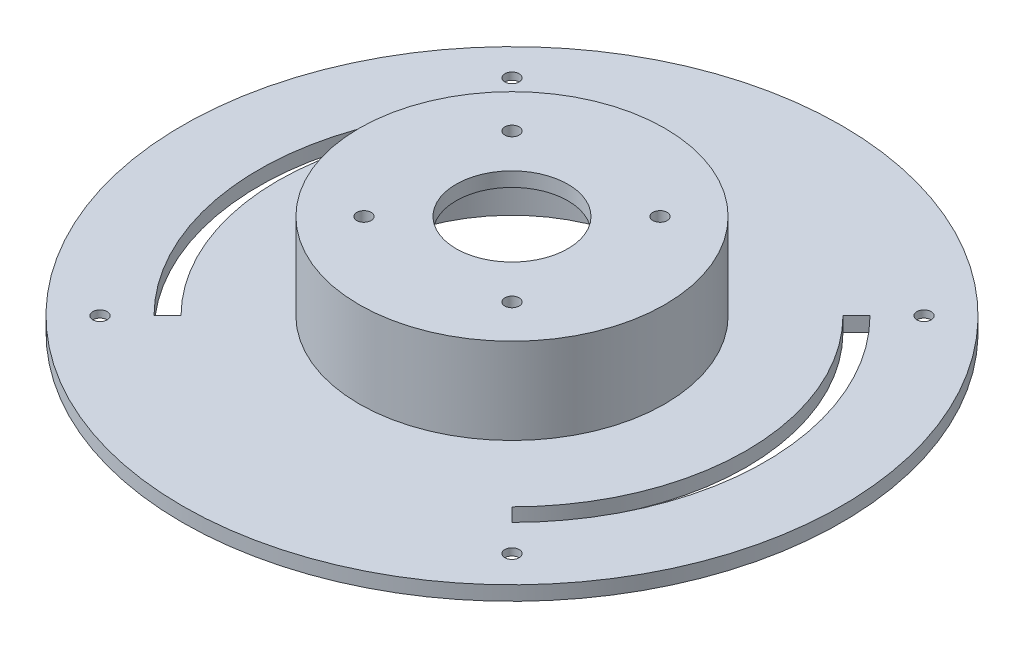
SolidWorks part; units mm, degrees
ref_plane "Front Plane" through (0, 0, 0) normal (0, 0, 1) x (1, 0, 0)
ref_plane "Top Plane" through (0, 0, 0) normal (0, 1, 0) x (1, 0, 0)
ref_plane "Right Plane" through (0, 0, 0) normal (1, 0, 0) x (0, 0, -1)
sketch "Sketch1" plane through (0, 0, 0) normal (0, 1, 0) x (1, 0, 0)
  circle A0 centre (0, 0) radius 69
  dimension "D1" = 138
extrude "Boss-Extrude1" add sketch "Sketch1" along normal blind 3
sketch "Sketch2" plane through (0, 3, 0) normal (0, 1, 0) x (1, 0, 0)
  circle A0 centre (0, 0) radius 32
  dimension "D1" = 64
extrude "Boss-Extrude2" add sketch "Sketch2" along normal blind 18
sketch "Sketch3" plane through (0, 21, 0) normal (0, 1, 0) x (1, 0, 0)
  line L0 (0, 56.364) -> (0, -54.6297) construction
  line L1 (-45.6693, 0) -> (37.576, 0) construction
  circle A0 centre (0, 0) radius 11.7
  circle A1 centre (15.5, 15.5) radius 1.5
  circle A2 centre (-15.5, 15.5) radius 1.5
  circle A3 centre (15.5, -15.5) radius 1.5
  circle A4 centre (-15.5, -15.5) radius 1.5
  dimension "D1" = 23.4
  dimension "D2" = 3
  dimension "D3" = 15.5
  dimension "D4" = 15.5
extrude "Cut-Extrude1" cut sketch "Sketch3" against normal through all
ref_plane "Plane2" through (0, 0, 0) normal (0, -1, 0) x (-1, 0, 0)
sketch "Sketch6" plane through (0, 0, 0) normal (0, -1, 0) x (-1, 0, 0)
  circle A0 centre (0, 0) radius 30
  dimension "D1" = 60
extrude "Cut-Extrude3" cut sketch "Sketch6" against normal blind 18
sketch "Sketch7" plane through (0, 3, 0) normal (0, 1, 0) x (1, 0, 0)
  line L0 (0, 73.7068) -> (0, -77.7534) construction
  line L1 (-89.2189, 0) -> (93.0728, 0) construction
  line L2 (0, 0) -> (55.0633, 55.0633) construction
  line L3 (0, 0) -> (-61.1332, 61.1332) construction
  line L4 (0, 0) -> (-63.9579, -63.9579) construction
  line L5 (0, 0) -> (64.7945, -64.7945) construction
  line L6 (34.6482, 34.6482) -> (37.4767, 37.4767)
  line L7 (37.4767, -37.4767) -> (34.6482, -34.6482)
  line L8 (-37.4767, -37.4767) -> (-34.6482, -34.6482)
  line L9 (-34.6482, 34.6482) -> (-37.4767, 37.4767)
  arc A0 (34.6482, 34.6482) -> (34.6482, -34.6482) centre (0, 0) cw
  circle A1 centre (0, 0) radius 69 construction
  arc A2 (37.4767, 37.4767) -> (37.4767, -37.4767) centre (0, 0) cw
  arc A3 (-34.6482, 34.6482) -> (-34.6482, -34.6482) centre (0, 0) ccw
  arc A4 (-37.4767, 37.4767) -> (-37.4767, -37.4767) centre (0, 0) ccw
  circle A5 centre (43.1335, 43.1335) radius 1.5
  circle A6 centre (43.1335, -43.1335) radius 1.5
  circle A7 centre (-43.1335, -43.1335) radius 1.5
  circle A8 centre (-43.1335, 43.1335) radius 1.5
  point P24 (0, 0)
  point P25 (0, 0)
  dimension "D5" = 20
  dimension "D7" = 12
  dimension "D8" = 3
  dimension "D1" = 45
  dimension "D2" = 45
  dimension "D3" = 45
  dimension "D4" = 45
  dimension "D6" = 4
extrude "Cut-Extrude5" cut sketch "Sketch7" against normal through all
sketch "Sketch8" plane through (0, 0, 0) normal (0, -1, 0) x (1, 0, 0)
  line L0 (0, 119.0407) -> (0, -90.7373) construction
  line L1 (-103.8901, 0) -> (87.907, 0) construction
  circle A0 centre (-43.1335, 43.1335) radius 4.05
  circle A1 centre (43.1335, 43.1335) radius 4.05
  circle A2 centre (43.1335, -43.1335) radius 4.05
  circle A3 centre (-43.1335, -43.1335) radius 4.05
  dimension "D1" = 8.1
extrude "Cut-Extrude6" cut sketch "Sketch8" against normal blind 1.5
